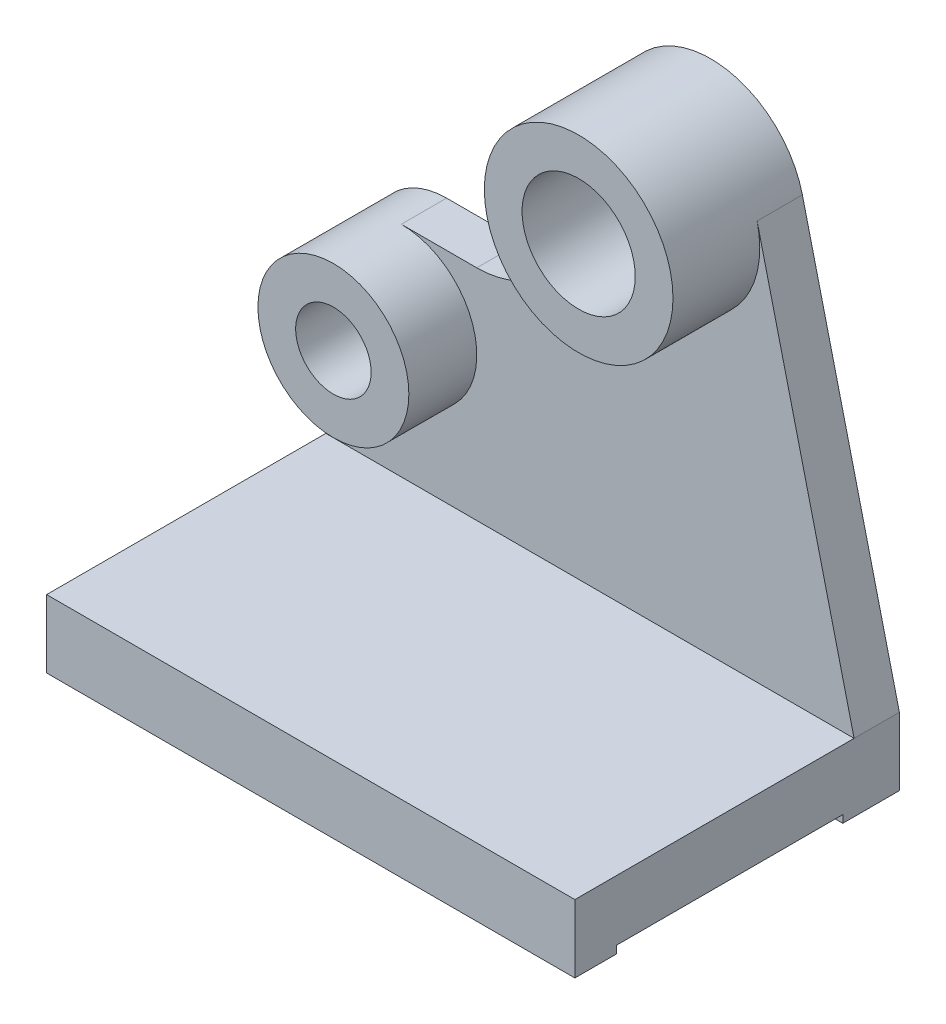
SolidWorks part; units mm, degrees
ref_plane "Front Plane" through (0, 0, 0) normal (0, 0, 1) x (1, 0, 0)
ref_plane "Top Plane" through (0, 0, 0) normal (0, 1, 0) x (1, 0, 0)
ref_plane "Right Plane" through (0, 0, 0) normal (1, 0, 0) x (0, 0, -1)
sketch "Sketch1" plane through (0, 0, 0) normal (0, 0, 1) x (1, 0, 0)
  line L0 (0, 0) -> (0, -10750.275) construction
  line L1 (0, 0) -> (-10750.275, 0) construction
  line L2 (50, 18) -> (24.2945, 123.8972)
  line L3 (-90, 18) -> (50, 18)
  line L4 (-90, 56) -> (-90, 0)
  line L5 (-90, 0) -> (50, 0)
  line L6 (50, 18) -> (50, 0)
  line L7 (-25, 118) -> (-25, 101)
  line L8 (-50, 76) -> (-70, 76)
  circle A0 centre (-70, 56) radius 10
  circle A1 centre (-70, 56) radius 20
  circle A2 centre (0, 118) radius 15
  circle A3 centre (0, 118) radius 25
  arc A4 (-25, 101) -> (-50, 76) centre (-50, 101) cw
  dimension "D4" = 20
  dimension "D5" = 40
  dimension "D6" = 30
  dimension "D7" = 50
  dimension "D10" = 25
  dimension "D1" = 140
  dimension "D2" = 50
  dimension "D3" = 18
  dimension "D8" = 118
  dimension "D9" = 56
extrude "Boss-Extrude1" add sketch "Sketch1" along normal blind 86 contours L6 L3 L4 L5 region at (-20, 9, 0)
extrude "Boss-Extrude2" add sketch "Sketch1<3>" along normal blind 12 contours L7 A4 L8 A1 L4 L3 L2 A3 region at (-10.5049, 52.5701, 0)
sketch "Sketch1<3>" plane through (0, 0, 0) normal (0, 0, 1) x (1, 0, 0) same geometry as "Sketch1"
extrude "Boss-Extrude3" add sketch "Sketch1<4>" along normal blind 35 contours A3 A2 region at (24.1209, 120.8857, 0)
sketch "Sketch1<4>" plane through (0, 0, 0) normal (0, 0, 1) x (1, 0, 0) same geometry as "Sketch1"
extrude "Boss-Extrude4" add sketch "Sketch1<5>" along normal blind 30 contours A1 A0 region at (-83.7421, 69.7421, 0)
sketch "Sketch1<5>" plane through (0, 0, 0) normal (0, 0, 1) x (1, 0, 0) same geometry as "Sketch1"
sketch "Sketch3" [suppressed] plane through (50, 0, 0) normal (1, 0, 0) x (0, 0, -1)
  line L0 (-86, 0) -> (0, 0) construction
  line L1 (-75, 2) -> (-15, 2)
  line L2 (-75, 2) -> (-75, 0)
  line L3 (-75, 0) -> (-15, 0)
  line L4 (-15, 2) -> (-15, 0)
  dimension "D1" = 60
  dimension "D2" = 2
  dimension "D3" = 15
extrude "Boss-Extrude7" [suppressed] add sketch "Sketch3" against normal up to next
sketch "Sketch4" plane through (50, 0, 0) normal (1, 0, 0) x (0, 0, -1)
  line L0 (-86, 0) -> (0, 0) construction
  line L1 (-75, 2) -> (-15, 2)
  line L2 (-75, 2) -> (-75, 0)
  line L3 (-75, 0) -> (-15, 0)
  line L4 (-15, 2) -> (-15, 0)
  dimension "D1" = 60
  dimension "D2" = 15
  dimension "D3" = 2
extrude "Cut-Extrude1" cut sketch "Sketch4" against normal up to next
